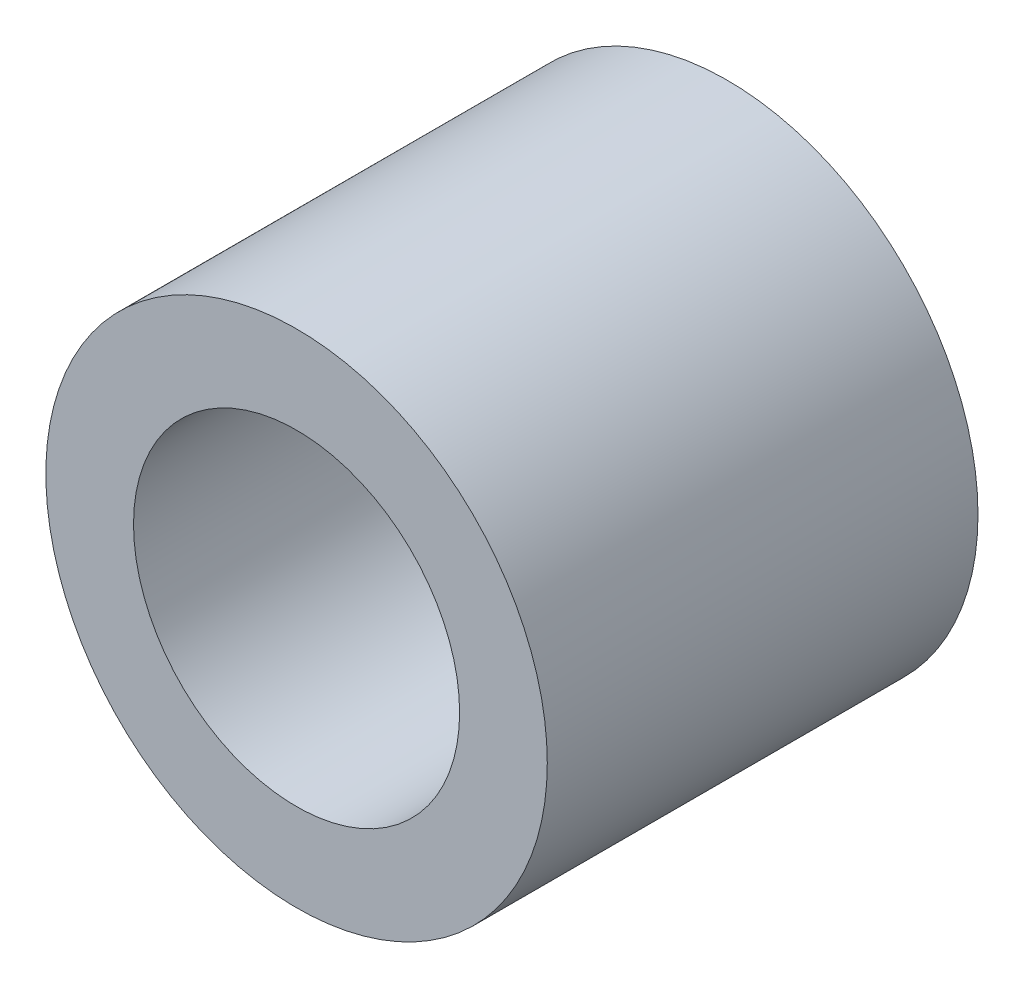
SolidWorks part; units mm, degrees
ref_plane "Top Plane" through (0, 0, 0) normal (0, 0, 1) x (1, 0, 0)
ref_plane "Right Plane" through (0, 0, 0) normal (0, 1, 0) x (1, 0, 0)
ref_plane "Front Plane" through (0, 0, 0) normal (1, 0, 0) x (0, 0, -1)
ref_axis "x-axis" through (-88.99, 0, 0) along (1, 0, 0)
ref_axis "y-axis" through (0, -55, 0) along (0, 1, 0)
ref_axis "z-axis" through (0, 0, 55) along (0, 0, -1)
sketch "Sketch1" plane through (0, 0, 0) normal (0, 0, 1) x (1, 0, 0)
  circle A0 centre (0, 0) radius 4.075
  dimension "D1" = 8.15
extrude "Boss-Extrude1" add sketch "Sketch1" along normal blind 7
hole_wizard "M5 Clearance Hole1" positions "Sketch2" profile "Sketch3" hole size "M5" standard "ANSI Metric" end condition through all
sketch "Sketch2" plane through (0, 0, 7) normal (0, 0, 1) x (1, 0, 0)
  point P0 (0, 0)
sketch "Sketch3" plane through (0, 0, 7) normal (1, 0, 0) x (0, -1, 0)
  line L0 (0, 0) -> (0, 7)
  line L1 (0, 7) -> (2.65, 7)
  line L2 (2.65, 7) -> (2.65, 0)
  line L5 (2.65, 0) -> (0, 0)
  line L11 (0, -6.35) -> (0, 107.95) construction
  dimension "Thru Hole Dia." = 5.3
  dimension "Thru Hole Depth" = 7
